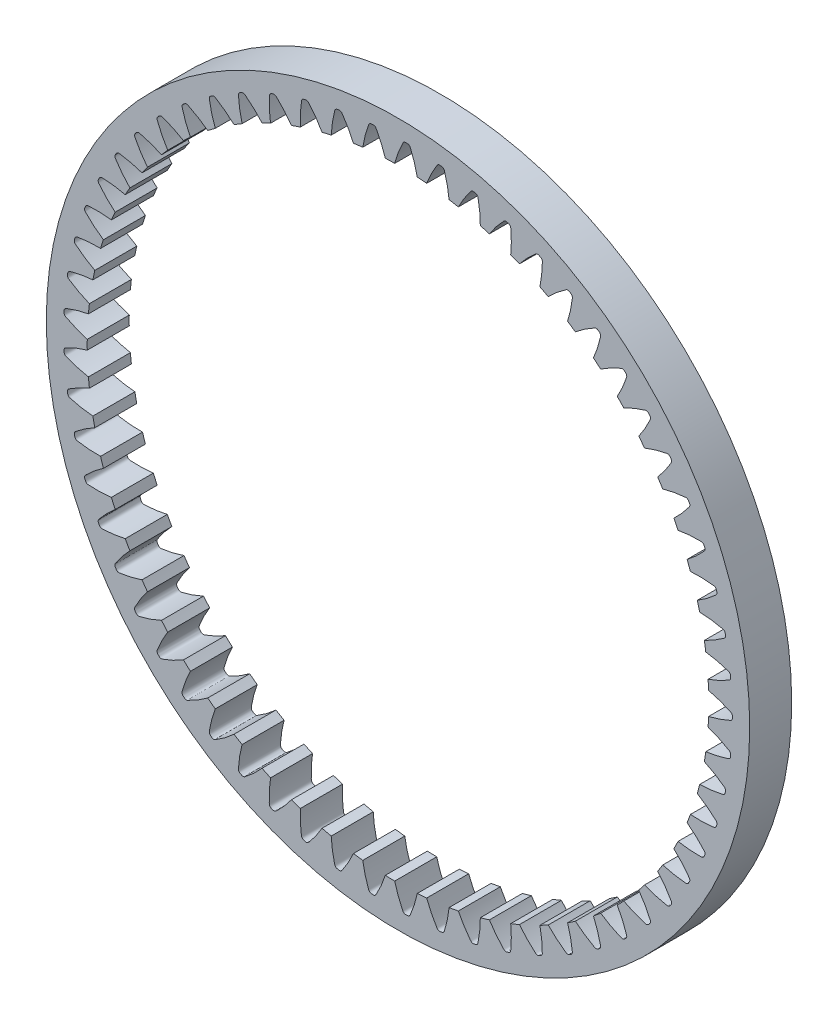
SolidWorks part; units mm, degrees
ref_plane "Front Plane" through (0, 0, 0) normal (0, 0, 1) x (1, 0, 0)
ref_plane "Top Plane" through (0, 0, 0) normal (0, 1, 0) x (1, 0, 0)
ref_plane "Right Plane" through (0, 0, 0) normal (1, 0, 0) x (0, 0, -1)
ref_axis "Axis1" through (0, 0, 55) along (0, 0, -1)
sketch "SketchRevolveSpurGear" plane through (0, 0, 0) normal (1, 0, 0) x (0, 0, -1)
  line L0 (0, 0) -> (1, 0) construction
  line L1 (-2, 29.6) -> (-2, 33.5)
  line L2 (-2, 33.5) -> (2, 33.5)
  line L3 (2, 33.5) -> (2, 29.6)
  line L4 (2, 29.6) -> (-2, 29.6)
  dimension "Side1" = 2
  dimension "OutsideRadius" = 33.5
  dimension "Side2" = 2
  dimension "MinorDiameter" = 29.6
revolve "SpurGear" add sketch "SketchRevolveSpurGear" angle 360 about L0
sketch "SketchToothSpurGear" plane through (0, 0, 0) normal (0, 0, 1) x (1, 0, 0)
  arc A0 (29.5619, -1.0793) -> (29.5619, 1.0793) centre (0, 0) ccw
  spline S0 degree 3 poles (29.5619, 1.0793) (29.6732, 1.0552) (29.8457, 1.0135) (30.0825, 0.9486) (30.278, 0.8904) (30.4848, 0.8239) (30.7028, 0.7487) (30.9314, 0.6641) (31.1708, 0.5703) (31.4194, 0.4641) (31.6036, 0.388) (31.7136, 0.3313) (31.7481, 0.3049) (31.7782, 0.2745) (31.8038, 0.2401) (31.8241, 0.2024) (31.8439, 0.1494) (31.8508, 0.0938) (31.8498, 0.0396) (31.8501, 0) (31.8498, -0.0396) (31.8508, -0.0938) (31.8439, -0.1494) (31.8241, -0.2024) (31.8038, -0.2401) (31.7782, -0.2745) (31.7481, -0.3049) (31.7136, -0.3313) (31.6036, -0.388) (31.4194, -0.4641) (31.1708, -0.5703) (30.9314, -0.6641) (30.7028, -0.7487) (30.4848, -0.8239) (30.278, -0.8904) (30.0825, -0.9486) (29.8457, -1.0135) (29.6732, -1.0552) (29.5619, -1.0793) knots 0 0 0 0 0.064237 0.100096 0.13845 0.179297 0.222639 0.268474 0.316804 0.367627 0.420945 0.429252 0.437279 0.445307 0.453334 0.461362 0.469389 0.485126 0.492563 0.5 0.507437 0.514874 0.530611 0.538638 0.546666 0.554693 0.562721 0.570748 0.579055 0.632373 0.683196 0.731526 0.777361 0.820703 0.86155 0.899904 0.935763 1 1 1 1
extrude "ToothExtrudeCutSpurGear" cut sketch "SketchToothSpurGear" against normal blind 2 and the other way blind 2
pattern_circular "PatternSpurGear" count 61 every 5.902 about axis through (0, 0, 55) along (0, 0, -1) of "ToothExtrudeCutSpurGear"
sketch "AuxiliarySketchSpurGear" plane through (0, 0, 0) normal (0, 0, 1) x (1, 0, 0)
  circle A0 centre (0, 0) radius 30.5 construction
  circle A1 centre (0, 0) radius 28.6606 construction
  circle A2 centre (0, 0) radius 31.85 construction
  circle A3 centre (0, 0) radius 29.6 construction
  dimension "PitchDiameter" = 61
  dimension "BaseDiameter" = 57.3212
  dimension "MajorDiameter" = 63.7
  dimension "MinorDiameter" = 59.2
